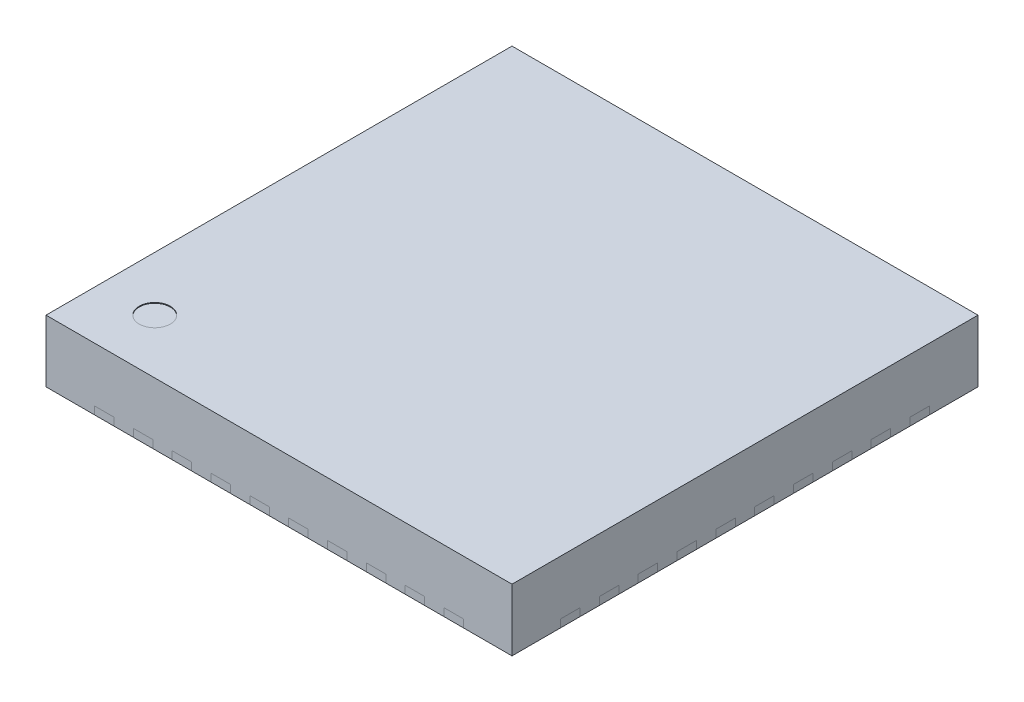
SolidWorks part; units mm, degrees
ref_plane "Спереди" through (0, 0, 0) normal (0, 0, 1) x (1, 0, 0)
ref_plane "Сверху" through (0, 0, 0) normal (0, 1, 0) x (1, 0, 0)
ref_plane "Справа" through (0, 0, 0) normal (1, 0, 0) x (0, 0, -1)
sketch "Эскиз1" plane through (0, 0, 0) normal (0, 1, 0) x (1, 0, 0)
  line L1 (-3, 3) -> (3, 3)
  line L2 (-3, 3) -> (-3, -3)
  line L3 (-3, -3) -> (3, -3)
  line L4 (3, 3) -> (3, -3)
  line L5 (-3, 3) -> (3, -3) construction
  line L6 (-3, -3) -> (3, 3) construction
  point P0 (0, 0)
  dimension "D1" = 6
extrude "Вытянуть1" add sketch "Эскиз1" along normal blind 0.8
sketch "Эскиз2" plane through (0, 0, 0) normal (0, -1, 0) x (1, 0, 0)
  line L0 (-3, 3) -> (3, 3) construction
  line L1 (-0.375, 2.6) -> (-0.125, 2.6)
  line L2 (-0.375, 2.6) -> (-0.375, 3)
  line L3 (-0.375, 3) -> (-0.125, 3)
  line L4 (-0.125, 2.6) -> (-0.125, 3)
  line L5 (-0.375, 2.6) -> (-0.125, 3) construction
  line L6 (-0.375, 3) -> (-0.125, 2.6) construction
  line L7 (0, -0.44) -> (0, 0.44) construction
  line L8 (-0.875, 2.6) -> (-0.625, 2.6)
  line L9 (-0.875, 2.6) -> (-0.875, 3)
  line L10 (-0.875, 3) -> (-0.625, 3)
  line L11 (-0.625, 2.6) -> (-0.625, 3)
  line L12 (-0.875, 2.6) -> (-0.625, 3) construction
  line L13 (-0.875, 3) -> (-0.625, 2.6) construction
  line L14 (-1.375, 2.6) -> (-1.125, 2.6)
  line L15 (-1.375, 2.6) -> (-1.375, 3)
  line L16 (-1.375, 3) -> (-1.125, 3)
  line L17 (-1.125, 2.6) -> (-1.125, 3)
  line L18 (-1.375, 2.6) -> (-1.125, 3) construction
  line L19 (-1.375, 3) -> (-1.125, 2.6) construction
  line L20 (-1.875, 2.6) -> (-1.625, 2.6)
  line L21 (-1.875, 2.6) -> (-1.875, 3)
  line L22 (-1.875, 3) -> (-1.625, 3)
  line L23 (-1.625, 2.6) -> (-1.625, 3)
  line L24 (-1.875, 2.6) -> (-1.625, 3) construction
  line L25 (-1.875, 3) -> (-1.625, 2.6) construction
  line L26 (-2.375, 2.6) -> (-2.125, 2.6)
  line L27 (-2.375, 2.6) -> (-2.375, 3)
  line L28 (-2.375, 3) -> (-2.125, 3)
  line L29 (-2.125, 2.6) -> (-2.125, 3)
  line L30 (-2.375, 2.6) -> (-2.125, 3) construction
  line L31 (-2.375, 3) -> (-2.125, 2.6) construction
  line L32 (-0.25, 2.8) -> (-0.75, 2.8) construction
  line L33 (0, 3) -> (0, -3) construction
  line L34 (3, -3) -> (-3, -3) construction
  line L35 (2.6, 0.375) -> (2.6, 0.125)
  line L36 (0.44, 0) -> (-0.44, 0) construction
  line L37 (-2.3, 2.05) -> (-2.05, 2.3)
  line L38 (0.25, 2.8) -> (0.75, 2.8) construction
  line L39 (2.375, 3) -> (2.125, 2.6) construction
  line L40 (2.375, 2.6) -> (2.125, 3) construction
  line L41 (1.875, 3) -> (1.625, 2.6) construction
  line L42 (1.875, 2.6) -> (1.625, 3) construction
  line L43 (1.375, 3) -> (1.125, 2.6) construction
  line L44 (1.375, 2.6) -> (1.125, 3) construction
  line L45 (0.875, 3) -> (0.625, 2.6) construction
  line L46 (0.875, 2.6) -> (0.625, 3) construction
  line L47 (0.375, 3) -> (0.125, 2.6) construction
  line L48 (0.375, 2.6) -> (0.125, 3) construction
  line L49 (2.125, 2.6) -> (2.125, 3)
  line L50 (2.375, 3) -> (2.125, 3)
  line L51 (2.375, 2.6) -> (2.375, 3)
  line L52 (2.375, 2.6) -> (2.125, 2.6)
  line L53 (1.625, 2.6) -> (1.625, 3)
  line L54 (1.875, 3) -> (1.625, 3)
  line L55 (1.875, 2.6) -> (1.875, 3)
  line L56 (1.875, 2.6) -> (1.625, 2.6)
  line L57 (1.125, 2.6) -> (1.125, 3)
  line L58 (1.375, 3) -> (1.125, 3)
  line L59 (1.375, 2.6) -> (1.375, 3)
  line L60 (1.375, 2.6) -> (1.125, 2.6)
  line L61 (0.625, 2.6) -> (0.625, 3)
  line L62 (0.875, 3) -> (0.625, 3)
  line L63 (0.875, 2.6) -> (0.875, 3)
  line L64 (0.875, 2.6) -> (0.625, 2.6)
  line L65 (0.125, 2.6) -> (0.125, 3)
  line L66 (0.375, 3) -> (0.125, 3)
  line L67 (0.375, 2.6) -> (0.375, 3)
  line L68 (0.375, 2.6) -> (0.125, 2.6)
  line L69 (2.6, 0.375) -> (3, 0.375)
  line L70 (3, 0.375) -> (3, 0.125)
  line L71 (2.6, 0.125) -> (3, 0.125)
  line L72 (2.6, 0.875) -> (2.6, 0.625)
  line L73 (2.6, 0.875) -> (3, 0.875)
  line L74 (3, 0.875) -> (3, 0.625)
  line L75 (2.6, 0.625) -> (3, 0.625)
  line L76 (2.6, 1.375) -> (2.6, 1.125)
  line L77 (2.6, 1.375) -> (3, 1.375)
  line L78 (3, 1.375) -> (3, 1.125)
  line L79 (2.6, 1.125) -> (3, 1.125)
  line L80 (2.6, 1.875) -> (2.6, 1.625)
  line L81 (2.6, 1.875) -> (3, 1.875)
  line L82 (3, 1.875) -> (3, 1.625)
  line L83 (2.6, 1.625) -> (3, 1.625)
  line L84 (2.6, 2.375) -> (2.6, 2.125)
  line L85 (2.6, 2.375) -> (3, 2.375)
  line L86 (3, 2.375) -> (3, 2.125)
  line L87 (2.6, 2.125) -> (3, 2.125)
  line L88 (2.6, -2.125) -> (3, -2.125)
  line L89 (3, -2.375) -> (3, -2.125)
  line L90 (2.6, -2.375) -> (3, -2.375)
  line L91 (2.6, -2.375) -> (2.6, -2.125)
  line L92 (2.6, -1.625) -> (3, -1.625)
  line L93 (3, -1.875) -> (3, -1.625)
  line L94 (2.6, -1.875) -> (3, -1.875)
  line L95 (2.6, -1.875) -> (2.6, -1.625)
  line L96 (2.6, -1.125) -> (3, -1.125)
  line L97 (3, -1.375) -> (3, -1.125)
  line L98 (2.6, -1.375) -> (3, -1.375)
  line L99 (2.6, -1.375) -> (2.6, -1.125)
  line L100 (2.6, -0.625) -> (3, -0.625)
  line L101 (3, -0.875) -> (3, -0.625)
  line L102 (2.6, -0.875) -> (3, -0.875)
  line L103 (2.6, -0.875) -> (2.6, -0.625)
  line L104 (2.6, -0.125) -> (3, -0.125)
  line L105 (3, -0.375) -> (3, -0.125)
  line L106 (2.6, -0.375) -> (3, -0.375)
  line L107 (2.6, -0.375) -> (2.6, -0.125)
  line L108 (2.6, 0.375) -> (3, 0.125) construction
  line L109 (3, 0.375) -> (2.6, 0.125) construction
  line L110 (2.6, 0.875) -> (3, 0.625) construction
  line L111 (3, 0.875) -> (2.6, 0.625) construction
  line L112 (2.6, 1.375) -> (3, 1.125) construction
  line L113 (3, 1.375) -> (2.6, 1.125) construction
  line L114 (2.6, 1.875) -> (3, 1.625) construction
  line L115 (3, 1.875) -> (2.6, 1.625) construction
  line L116 (2.6, 2.375) -> (3, 2.125) construction
  line L117 (3, 2.375) -> (2.6, 2.125) construction
  line L118 (2.8, 0.25) -> (2.8, 0.75) construction
  line L119 (2.8, -0.25) -> (2.8, -0.75) construction
  line L120 (3, -2.375) -> (2.6, -2.125) construction
  line L121 (2.6, -2.375) -> (3, -2.125) construction
  line L122 (3, -1.875) -> (2.6, -1.625) construction
  line L123 (2.6, -1.875) -> (3, -1.625) construction
  line L124 (3, -1.375) -> (2.6, -1.125) construction
  line L125 (2.6, -1.375) -> (3, -1.125) construction
  line L126 (3, -0.875) -> (2.6, -0.625) construction
  line L127 (2.6, -0.875) -> (3, -0.625) construction
  line L128 (3, -0.375) -> (2.6, -0.125) construction
  line L129 (2.6, -0.375) -> (3, -0.125) construction
  line L130 (0.375, -2.6) -> (0.125, -2.6)
  line L131 (0.375, -2.6) -> (0.375, -3)
  line L132 (0.375, -3) -> (0.125, -3)
  line L133 (0.125, -2.6) -> (0.125, -3)
  line L134 (0.875, -2.6) -> (0.625, -2.6)
  line L135 (0.875, -2.6) -> (0.875, -3)
  line L136 (0.875, -3) -> (0.625, -3)
  line L137 (0.625, -2.6) -> (0.625, -3)
  line L138 (1.375, -2.6) -> (1.125, -2.6)
  line L139 (1.375, -2.6) -> (1.375, -3)
  line L140 (1.375, -3) -> (1.125, -3)
  line L141 (1.125, -2.6) -> (1.125, -3)
  line L142 (1.875, -2.6) -> (1.625, -2.6)
  line L143 (1.875, -2.6) -> (1.875, -3)
  line L144 (1.875, -3) -> (1.625, -3)
  line L145 (1.625, -2.6) -> (1.625, -3)
  line L146 (2.375, -2.6) -> (2.125, -2.6)
  line L147 (2.375, -2.6) -> (2.375, -3)
  line L148 (2.375, -3) -> (2.125, -3)
  line L149 (2.125, -2.6) -> (2.125, -3)
  line L150 (-2.125, -2.6) -> (-2.125, -3)
  line L151 (-2.375, -3) -> (-2.125, -3)
  line L152 (-2.375, -2.6) -> (-2.375, -3)
  line L153 (-2.375, -2.6) -> (-2.125, -2.6)
  line L154 (-1.625, -2.6) -> (-1.625, -3)
  line L155 (-1.875, -3) -> (-1.625, -3)
  line L156 (-1.875, -2.6) -> (-1.875, -3)
  line L157 (-1.875, -2.6) -> (-1.625, -2.6)
  line L158 (-1.125, -2.6) -> (-1.125, -3)
  line L159 (-1.375, -3) -> (-1.125, -3)
  line L160 (-1.375, -2.6) -> (-1.375, -3)
  line L161 (-1.375, -2.6) -> (-1.125, -2.6)
  line L162 (-0.625, -2.6) -> (-0.625, -3)
  line L163 (-0.875, -3) -> (-0.625, -3)
  line L164 (-0.875, -2.6) -> (-0.875, -3)
  line L165 (-0.875, -2.6) -> (-0.625, -2.6)
  line L166 (-0.125, -2.6) -> (-0.125, -3)
  line L167 (-0.375, -3) -> (-0.125, -3)
  line L168 (-0.375, -2.6) -> (-0.375, -3)
  line L169 (-0.375, -2.6) -> (-0.125, -2.6)
  line L170 (0.375, -2.6) -> (0.125, -3) construction
  line L171 (0.375, -3) -> (0.125, -2.6) construction
  line L172 (0.875, -2.6) -> (0.625, -3) construction
  line L173 (0.875, -3) -> (0.625, -2.6) construction
  line L174 (1.375, -2.6) -> (1.125, -3) construction
  line L175 (1.375, -3) -> (1.125, -2.6) construction
  line L176 (1.875, -2.6) -> (1.625, -3) construction
  line L177 (1.875, -3) -> (1.625, -2.6) construction
  line L178 (2.375, -2.6) -> (2.125, -3) construction
  line L179 (2.375, -3) -> (2.125, -2.6) construction
  line L180 (0.25, -2.8) -> (0.75, -2.8) construction
  line L181 (-0.25, -2.8) -> (-0.75, -2.8) construction
  line L182 (-2.375, -3) -> (-2.125, -2.6) construction
  line L183 (-2.375, -2.6) -> (-2.125, -3) construction
  line L184 (-1.875, -3) -> (-1.625, -2.6) construction
  line L185 (-1.875, -2.6) -> (-1.625, -3) construction
  line L186 (-1.375, -3) -> (-1.125, -2.6) construction
  line L187 (-1.375, -2.6) -> (-1.125, -3) construction
  line L188 (-0.875, -3) -> (-0.625, -2.6) construction
  line L189 (-0.875, -2.6) -> (-0.625, -3) construction
  line L190 (-0.375, -3) -> (-0.125, -2.6) construction
  line L191 (-0.375, -2.6) -> (-0.125, -3) construction
  line L192 (-2.6, -0.375) -> (-2.6, -0.125)
  line L193 (-2.6, -0.375) -> (-3, -0.375)
  line L194 (-3, -0.375) -> (-3, -0.125)
  line L195 (-2.6, -0.125) -> (-3, -0.125)
  line L196 (-2.6, -0.875) -> (-2.6, -0.625)
  line L197 (-2.6, -0.875) -> (-3, -0.875)
  line L198 (-3, -0.875) -> (-3, -0.625)
  line L199 (-2.6, -0.625) -> (-3, -0.625)
  line L200 (-2.6, -1.375) -> (-2.6, -1.125)
  line L201 (-2.6, -1.375) -> (-3, -1.375)
  line L202 (-3, -1.375) -> (-3, -1.125)
  line L203 (-2.6, -1.125) -> (-3, -1.125)
  line L204 (-2.6, -1.875) -> (-2.6, -1.625)
  line L205 (-2.6, -1.875) -> (-3, -1.875)
  line L206 (-3, -1.875) -> (-3, -1.625)
  line L207 (-2.6, -1.625) -> (-3, -1.625)
  line L208 (-2.6, -2.375) -> (-2.6, -2.125)
  line L209 (-2.6, -2.375) -> (-3, -2.375)
  line L210 (-3, -2.375) -> (-3, -2.125)
  line L211 (-2.6, -2.125) -> (-3, -2.125)
  line L212 (-2.6, 2.125) -> (-3, 2.125)
  line L213 (-3, 2.375) -> (-3, 2.125)
  line L214 (-2.6, 2.375) -> (-3, 2.375)
  line L215 (-2.6, 2.375) -> (-2.6, 2.125)
  line L216 (-2.6, 1.625) -> (-3, 1.625)
  line L217 (-3, 1.875) -> (-3, 1.625)
  line L218 (-2.6, 1.875) -> (-3, 1.875)
  line L219 (-2.6, 1.875) -> (-2.6, 1.625)
  line L220 (-2.6, 1.125) -> (-3, 1.125)
  line L221 (-3, 1.375) -> (-3, 1.125)
  line L222 (-2.6, 1.375) -> (-3, 1.375)
  line L223 (-2.6, 1.375) -> (-2.6, 1.125)
  line L224 (-2.6, 0.625) -> (-3, 0.625)
  line L225 (-3, 0.875) -> (-3, 0.625)
  line L226 (-2.6, 0.875) -> (-3, 0.875)
  line L227 (-2.6, 0.875) -> (-2.6, 0.625)
  line L228 (-2.6, 0.125) -> (-3, 0.125)
  line L229 (-3, 0.375) -> (-3, 0.125)
  line L230 (-2.6, 0.375) -> (-3, 0.375)
  line L231 (-2.6, 0.375) -> (-2.6, 0.125)
  line L232 (-2.6, -0.375) -> (-3, -0.125) construction
  line L233 (-3, -0.375) -> (-2.6, -0.125) construction
  line L234 (-2.6, -0.875) -> (-3, -0.625) construction
  line L235 (-3, -0.875) -> (-2.6, -0.625) construction
  line L236 (-2.6, -1.375) -> (-3, -1.125) construction
  line L237 (-3, -1.375) -> (-2.6, -1.125) construction
  line L238 (-2.6, -1.875) -> (-3, -1.625) construction
  line L239 (-3, -1.875) -> (-2.6, -1.625) construction
  line L240 (-2.6, -2.375) -> (-3, -2.125) construction
  line L241 (-3, -2.375) -> (-2.6, -2.125) construction
  line L242 (-2.8, -0.25) -> (-2.8, -0.75) construction
  line L243 (-2.8, 0.25) -> (-2.8, 0.75) construction
  line L244 (-3, 2.375) -> (-2.6, 2.125) construction
  line L245 (-2.6, 2.375) -> (-3, 2.125) construction
  line L246 (-3, 1.875) -> (-2.6, 1.625) construction
  line L247 (-2.6, 1.875) -> (-3, 1.625) construction
  line L248 (-3, 1.375) -> (-2.6, 1.125) construction
  line L249 (-2.6, 1.375) -> (-3, 1.125) construction
  line L250 (-3, 0.875) -> (-2.6, 0.625) construction
  line L251 (-2.6, 0.875) -> (-3, 0.625) construction
  line L252 (-3, 0.375) -> (-2.6, 0.125) construction
  line L253 (-2.6, 0.375) -> (-3, 0.125) construction
  line L254 (0, 0) -> (0.125, 2.6) construction
  line L255 (0, 0) -> (2.6, -0.125) construction
  line L256 (-2.05, 2.3) -> (2.3, 2.3)
  line L257 (-2.3, 2.05) -> (-2.3, -2.3)
  line L258 (-2.3, -2.3) -> (2.3, -2.3)
  line L259 (2.3, 2.3) -> (2.3, -2.3)
  line L260 (-2.3, 2.3) -> (2.3, -2.3) construction
  line L261 (-2.3, -2.3) -> (2.3, 2.3) construction
  point P0 (-0.25, 2.8)
  point P11 (-0.75, 2.8)
  point P16 (-1.25, 2.8)
  point P21 (-1.75, 2.8)
  point P26 (-2.25, 2.8)
  point P38 (2.8, 0.25)
  point P64 (2.25, 2.8)
  point P65 (1.75, 2.8)
  point P66 (1.25, 2.8)
  point P69 (2.8, 0.75)
  point P74 (2.8, 1.25)
  point P79 (2.8, 1.75)
  point P84 (2.8, 2.25)
  point P113 (2.8, -2.25)
  point P114 (2.8, -1.75)
  point P115 (2.8, -1.25)
  point P116 (0.25, -2.8)
  point P121 (0.75, -2.8)
  point P126 (1.25, -2.8)
  point P131 (1.75, -2.8)
  point P136 (2.25, -2.8)
  point P165 (-2.25, -2.8)
  point P166 (-1.75, -2.8)
  point P167 (-1.25, -2.8)
  point P168 (-2.8, -0.25)
  point P173 (-2.8, -0.75)
  point P178 (-2.8, -1.25)
  point P183 (-2.8, -1.75)
  point P188 (-2.8, -2.25)
  point P217 (-2.8, 2.25)
  point P218 (-2.8, 1.75)
  point P219 (-2.8, 1.25)
  dimension "D1" = 0.25
  dimension "D2" = 0.25
  dimension "D3" = 0.4
  dimension "D4" = 0.5
  dimension "D5" = 90
  dimension "D6" = 2.603
  dimension "D7" = 87.248
  dimension "D8" = 4.6
  dimension "D9" = 4.6
extrude "Вытянуть2" cut sketch "Эскиз2" against normal blind 0.1
extrude "Вытянуть3" add sketch "Эскиз2<3>" against normal up to next (0.1 mm away) separate body
sketch "Эскиз2<3>" plane through (0, 0, 0) normal (0, -1, 0) x (1, 0, 0) same geometry as "Эскиз2"
sketch "Эскиз3" plane through (0, 0.8, 0) normal (0, 1, 0) x (1, 0, 0)
  line L0 (-3, -3) -> (3, -3) construction
  line L2 (-3, 3) -> (-3, -3) construction
  circle A0 centre (-2.3, -2.3) radius 0.2
  dimension "D3" = 0.4
  dimension "D1" = 0.7
  dimension "D2" = 0.7
extrude "Вытянуть4" cut sketch "Эскиз3" against normal blind 0.01
